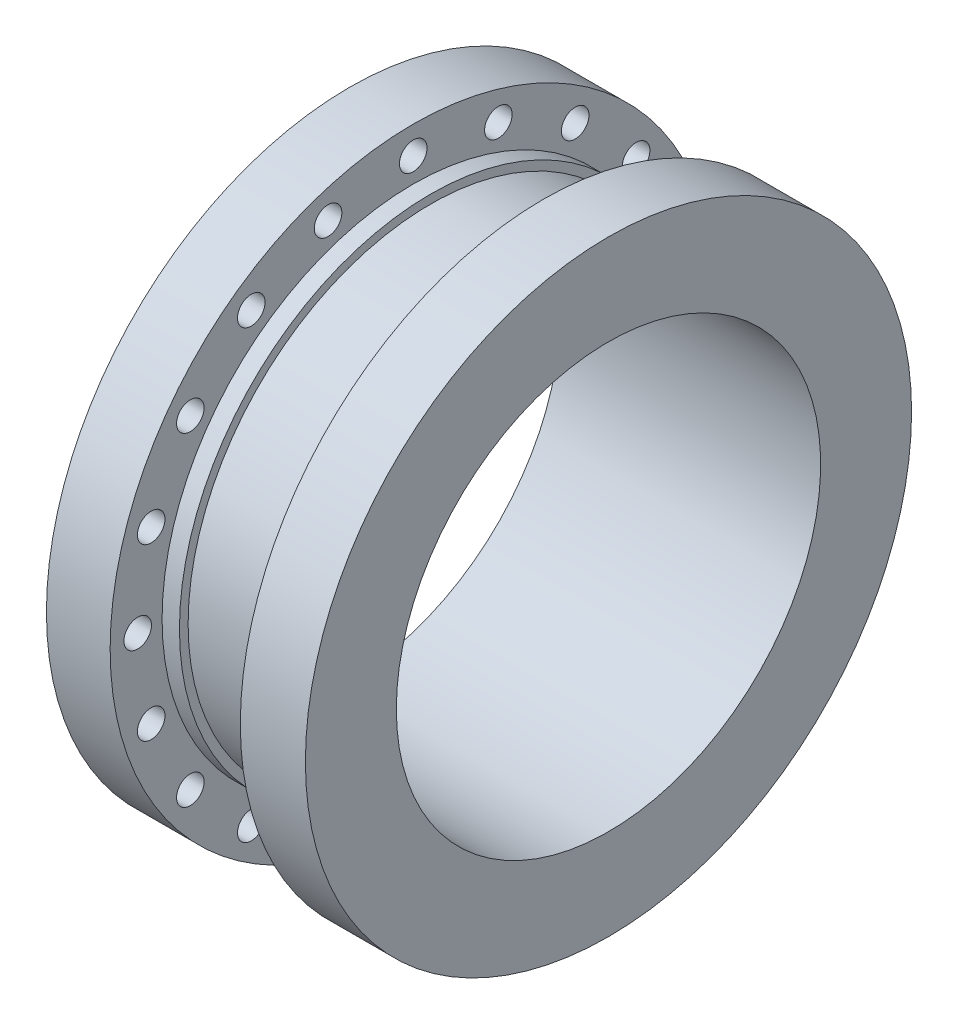
SolidWorks part; units mm, degrees
material "A105 N"
ref_plane "Front Plane" through (0, 0, 0) normal (0, 0, 1) x (1, 0, 0)
ref_plane "Top Plane" through (0, 0, 0) normal (0, 1, 0) x (1, 0, 0)
ref_plane "Right Plane" through (0, 0, 0) normal (1, 0, 0) x (0, 0, -1)
sketch "Sketch1" plane through (0, 0, 0) normal (0, 0, 1) x (1, 0, 0)
  line B0 (0, 0) -> (1975.6104, 0) construction
  line B1 (1740.0365, 0) -> (1740.0365, -350)
  line B2 (1725.0365, -350) -> (1740.0365, -350)
  line B3 (1725.0365, -210.5) -> (1725.0365, -350)
  line B4 (1705.0365, -190.5) -> (1725.0365, -210.5)
  line B5 (1690.0365, -190.5) -> (1705.0365, -190.5)
  line B6 (1690.0365, -190.5) -> (1390.0365, -190.5)
  line B7 (1390.0365, -190.5) -> (770.0365, -190.5)
  line B8 (770.0365, -190.5) -> (770.0365, 0)
sketch_block_instance "Inlret nozzle-1"
sketch_block "Inlret nozzle" parameters "D1"=620, "D2"=1390.0365, "D3"=15, "D4"=28.2843, "D5"=15, "D6"=45, "D7"=15, "D8"=350, "D9"=254, "D10"=350
sketch "Sketch2" plane through (0, 0, 0) normal (0, 0, 1) x (1, 0, 0)
  line L2 (1725.0365, -210.5) -> (1725.0365, -350) construction
  line L4 (1800.0365, -289.4) -> (1820.0365, -289.4)
  line L6 (1820.0365, -289.4) -> (1820.0365, -279.4)
  line L7 (1820.0365, -279.4) -> (1930.0365, -279.4)
  line L8 (1800.0365, -289.4) -> (1800.0365, -349.25)
  line L9 (1725.0365, -349.25) -> (1800.0365, -349.25)
  line L10 (1725.0365, -244.475) -> (1725.0365, -349.25)
  line L16 (0, 0) -> (1975.6104, 0) construction
  line L17 (0, 0) -> (1975.6104, 0) construction
  line L18 (1725.0365, 0) -> (1725.0365, -244.475) construction
  line L19 (1930.0365, -279.4) -> (1950.0365, -299.4)
  line L20 (1725.0365, 0) -> (1740.0365, 0) construction
  line L21 (1950.0365, -299.4) -> (1950.0365, -349.25)
  line L27 (0, 0) -> (1975.6104, 0) construction
  line L28 (1725.0365, -244.475) -> (1740.0365, -244.475)
  line L29 (1740.0365, 0) -> (1740.0365, -244.475) construction
  line L30 (1950.0365, -349.25) -> (2025.0365, -349.25)
  line L31 (2025.0365, -349.25) -> (2025.0365, -244.475)
  line L32 (2025.0365, -244.475) -> (1740.0365, -244.475)
  dimension "D1" = 244.475
  dimension "D2" = 75
  dimension "D3" = 300
  dimension "D4" = 135
  dimension "D5" = 20
  dimension "D6" = 279.4
  dimension "D7" = 10
  dimension "D8" = 20
  dimension "D9" = 349.25
  dimension "D10" = 15
  dimension "D11" = 75
revolve "Revolve1" add sketch "Sketch2" angle 360 about L17 region at (1796.8588, -319.325, 0)
sketch "Sketch3" plane through (1725.0365, 0, 0) normal (1, 0, 0) x (0, 0, -1)
  circle A0 centre (0, 0) radius 317.5 construction
  point P3 (0, 317.5)
  point P4 (98.1129, 301.9604)
  point P5 (-186.6218, -256.8629)
  point P6 (-256.8629, -186.6218)
  point P7 (186.6218, 256.8629)
  point P8 (256.8629, 186.6218)
  point P9 (301.9604, 98.1129)
  point P10 (317.5, 0)
  point P11 (301.9604, -98.1129)
  point P12 (256.8629, -186.6218)
  point P13 (186.6218, -256.8629)
  point P14 (98.1129, -301.9604)
  point P15 (0, -317.5)
  point P16 (-98.1129, -301.9604)
  point P17 (0, 0)
  point P18 (-301.9604, -98.1129)
  point P19 (-317.5, 0)
  point P20 (-301.9604, 98.1129)
  point P21 (-256.8629, 186.6218)
  point P22 (-186.6218, 256.8629)
  point P23 (-98.1129, 301.9604)
  dimension "D1" = 635
  dimension "D2" = 20
hole_wizard "Ø25.0mm Dowel Hole1" positions "3DSketch1" profile "Sketch4" hole size "Ø25.0" standard "ANSI Metric"
sketch3d "3DSketch1"
  circle A0 centre (1725.0365, 0, 0) radius 317.5 construction
  point P0 (1725.0365, 317.5, 0)
  point P3 (1725.0365, 301.9604, -98.1129)
  point P6 (1725.0365, 256.8629, -186.6218)
  point P9 (1725.0365, 186.6218, -256.8629)
  point P12 (1725.0365, 98.1129, -301.9604)
  point P15 (1725.0365, 0, -317.5)
  point P18 (1725.0365, -98.1129, -301.9604)
  point P21 (1725.0365, -186.6218, -256.8629)
  point P24 (1725.0365, -256.8629, -186.6218)
  point P27 (1725.0365, -301.9604, -98.1129)
  point P30 (1725.0365, -317.5, 0)
  point P33 (1725.0365, -301.9604, 98.1129)
  point P36 (1725.0365, 301.9604, 98.1129)
  point P39 (1725.0365, 256.8629, 186.6218)
  point P43 (2042.5365, 0, 0)
  point P44 (1725.0365, 186.6218, 256.8629)
  point P47 (1725.0365, 98.1129, 301.9604)
  point P50 (1725.0365, 0, 317.5)
  point P53 (1725.0365, -98.1129, 301.9604)
  point P56 (1725.0365, -186.6218, 256.8629)
  point P59 (1725.0365, -256.8629, 186.6218)
sketch "Sketch4" plane through (1725.0365, 317.5, 0) normal (0, 1, 0) x (0, 0, 1)
  line L0 (0, 0) -> (0, 87.7087)
  line L1 (0, 87.7087) -> (15.875, 78.17)
  line L2 (15.875, 78.17) -> (15.875, 0)
  line L5 (15.875, 0) -> (0, 0)
  line L10 (0, 87.7087) -> (-15.875, 78.17) construction
  line L11 (0, -6.35) -> (0, 107.95) construction
  dimension "Hole Dia." = 31.75
  dimension "Hole Depth" = 78.17
  dimension "Drill Angle" = 118
sketch "Sketch5" plane through (1725.0365, 0, 0) normal (-1, 0, 0) x (0, 0, 1)
  circle A0 centre (0, 0) radius 292.1
  circle A1 centre (0, 0) radius 349.25
  circle A2 centre (0, 0) radius 349.25
  dimension "D2" = 584.2
  dimension "D1" = 0
extrude "Cut-Extrude1" cut sketch "Sketch5" against normal blind 1.5875
